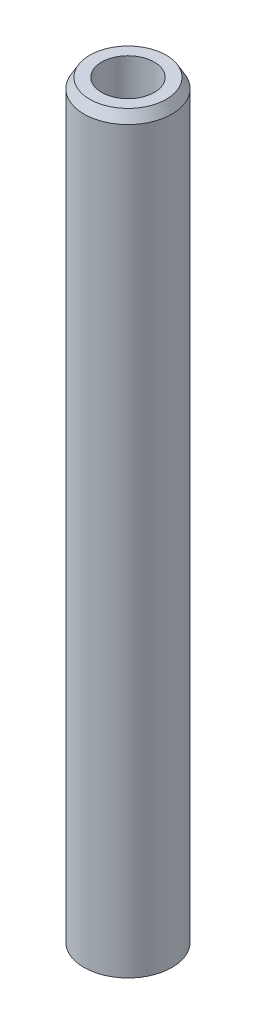
SolidWorks part; units mm, degrees
ref_plane "Front Plane" through (0, 0, 0) normal (0, 0, 1) x (1, 0, 0)
ref_plane "Top Plane" through (0, 0, 0) normal (0, 1, 0) x (1, 0, 0)
ref_plane "Right Plane" through (0, 0, 0) normal (1, 0, 0) x (0, 0, -1)
sketch "Sketch1" plane through (0, 0, 0) normal (0, 1, 0) x (1, 0, 0)
  circle A0 centre (0, 0) radius 25
  dimension "SHAFT_OD" = 50
extrude "Boss-Extrude1" add sketch "Sketch1" along normal blind 428.9669
sketch "Sketch2" plane through (0, 0, 0) normal (0, 1, 0) x (1, 0, 0)
  circle A0 centre (0, 0) radius 14.9669
  dimension "BORE_D" = 29.9339
extrude "Cut-Extrude1" cut sketch "Sketch2" along normal through all
chamfer "Chamfer1" distance 5.6537 angle 30 2 edges at (0, 428.9669, 25) (0, 0, 25) first distance on face at (0, 428.9669, 25) first distance on face at (0, 0, 14.9669)
